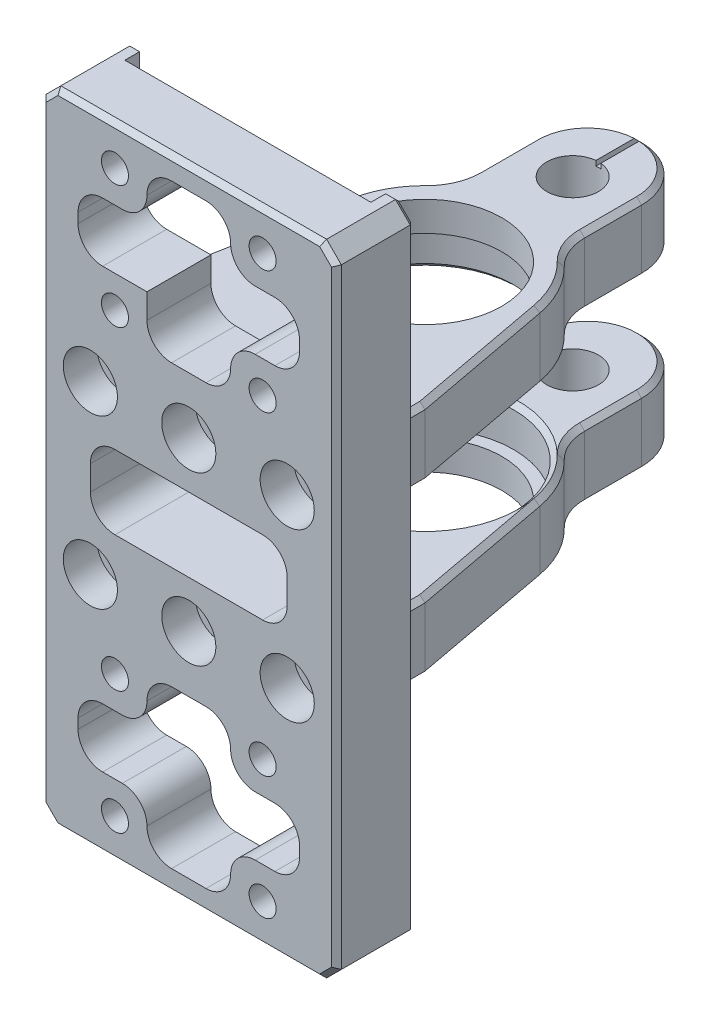
SolidWorks part; units mm, degrees
material "Q235-A"
ref_plane "前视基准面" through (0, 0, 0) normal (0, 0, 1) x (1, 0, 0)
ref_plane "上视基准面" through (0, 0, 0) normal (0, 1, 0) x (1, 0, 0)
ref_plane "右视基准面" through (0, 0, 0) normal (1, 0, 0) x (0, 0, -1)
sketch "草图1" plane through (0, 0, 0) normal (0, 0, 1) x (1, 0, 0)
  line L1 (-30, 65) -> (30, 65)
  line L2 (-30, 65) -> (-30, -65)
  line L3 (-30, -65) -> (30, -65)
  line L4 (30, 65) -> (30, -65)
  line L5 (-30, 65) -> (30, -65) construction
  line L6 (-30, -65) -> (30, 65) construction
  point P0 (0, 0)
  dimension "D1" = 60
  dimension "D2" = 130
extrude "凸台-拉伸1" add sketch "草图1" along normal blind 16
sketch "草图2" plane through (0, 0, 0) normal (0, 0, -1) x (-1, 0, 0)
  line L0 (0, -37.5) -> (0, 37.5) construction
  line L1 (30, -65) -> (-30, -65) construction
  line L2 (25, -65) -> (-25, -65)
  line L3 (25, -65) -> (25, -10)
  line L4 (25, -10) -> (-25, -10)
  line L5 (-25, -65) -> (-25, -10)
  line L6 (25, -65) -> (-25, -10) construction
  line L7 (25, -10) -> (-25, -65) construction
  line L8 (25, 10) -> (-25, 10)
  line L9 (25, 10) -> (25, 65)
  line L10 (25, 65) -> (-25, 65)
  line L11 (-25, 10) -> (-25, 65)
  line L12 (25, 10) -> (-25, 65) construction
  line L13 (25, 65) -> (-25, 10) construction
  point P4 (0, 0)
  dimension "D1" = 20
  dimension "D3" = 50
extrude "切除-拉伸1" cut sketch "草图2" against normal blind 3
sketch "草图14" plane through (0, 0, 0) normal (0, 0, -1) x (-1, 0, 0)
  circle A0 centre (-25, -10) radius 2.5
  circle A1 centre (-25, 10) radius 2.5
  circle A2 centre (25, 10) radius 2.5
  circle A3 centre (25, -10) radius 2.5
  dimension "D1" = 5
extrude "切除-拉伸5" cut sketch "草图14" against normal up to surface (3 mm away) up to face at (0, -37.5, 3)
sketch "草图4" plane through (0, 10, 0) normal (0, 1, 0) x (1, 0, 0)
  line L0 (25, -3) -> (25, 7)
  line L1 (-25, -3) -> (-25, 7)
  line L2 (25, -3) -> (-25, -3)
  line L3 (0, -3) -> (0, 32) construction
  line L4 (25, 7) -> (19.6619, 35.6619)
  line L5 (-25, 7) -> (-19.6619, 35.6619)
  arc A0 (19.6619, 35.6619) -> (-19.6619, 35.6619) centre (0, 32) ccw
  arc A1 (0, 12) -> (19.6619, 35.6619) centre (0, 32) ccw construction
  arc A2 (-19.6619, 35.6619) -> (0, 12) centre (0, 32) ccw construction
  dimension "D2" = 40
  dimension "D1" = 10
  dimension "D3" = 35
extrude "凸台-拉伸2" add sketch "草图4" along normal blind 14 separate body
sketch "草图7" plane through (0, 24, 0) normal (0, 1, 0) x (1, 0, 0)
  line L0 (0, 39) -> (0, 65) construction
  line L1 (-11, 39) -> (-11, 65)
  line L2 (11, 39) -> (11, 65)
  arc A0 (19.6619, 35.6619) -> (-19.6619, 35.6619) centre (0, 32) ccw construction
  arc A1 (-11, 39) -> (11, 39) centre (0, 39) ccw
  arc A2 (11, 65) -> (-11, 65) centre (0, 65) ccw
  point P7 (0, 52)
  dimension "D1" = 26
  dimension "D2" = 22
extrude "凸台-拉伸3" add sketch "草图7" against normal up to surface (14 mm away) up to face at (0, 10, -15.9437)
fillet "圆角1" radius 10 2 edges at (-11, 17, -48.7033) (11, 17, -48.7033)
sketch "草图5" plane through (0, 10, 0) normal (0, -1, 0) x (1, 0, 0)
  circle A0 centre (0, -32) radius 18
  dimension "D1" = 36
extrude "切除-拉伸2" cut sketch "草图5" against normal blind 8
sketch "草图6" plane through (0, 18, 0) normal (0, -1, 0) x (1, 0, 0)
  circle A0 centre (0, -32) radius 15.6
  dimension "D1" = 31.2
extrude "切除-拉伸3" cut sketch "草图6" against normal through all
hole_wizard "M12x1.5 螺纹孔1" positions "草图11" profile "草图12" tap size "M12x1.5" standard "GB"
sketch "草图11" plane through (0, 24, 0) normal (0, 1, 0) x (1, 0, 0)
  circle A0 centre (0, 32) radius 15.6 construction
  point P0 (0, 62)
  dimension "D1" = 30
sketch "草图12" plane through (0, 24, -62) normal (1, 0, 0) x (0, 0, 1)
  line L0 (0, 0) -> (0, 31.6545)
  line L1 (0, 31.6545) -> (5.25, 28.5)
  line L2 (5.25, 28.5) -> (5.25, 0)
  line L5 (5.25, 0) -> (0, 0)
  line L10 (0, 31.6545) -> (-5.25, 28.5) construction
  line L11 (0, -6.35) -> (0, 107.95) construction
  dimension "螺纹孔钻头直径" = 10.5
  dimension "螺纹孔钻头深度" = 28.5
  dimension "导头角度" = 118
cosmetic thread "孔螺蚊线1" parameters "D1"=24, "D2"=12
sketch "草图13" plane through (0, 24, 0) normal (0, 1, 0) x (1, 0, 0)
  line L0 (0, 84.75) -> (0, 67.25) construction
  line L1 (0.5, 84.75) -> (0.5, 67.25)
  line L2 (-0.5, 84.75) -> (-0.5, 67.25)
  arc A0 (11, 65) -> (-11, 65) centre (0, 65) ccw construction
  circle A1 centre (0, 62) radius 5.25 construction
  arc A2 (0.5, 84.75) -> (-0.5, 84.75) centre (0, 84.75) ccw
  arc A3 (-0.5, 67.25) -> (0.5, 67.25) centre (0, 67.25) ccw
  point P8 (0, 76)
  dimension "D1" = 1
extrude "切除-拉伸4" cut sketch "草图13" against normal blind 1
mirror "镜向2" about plane through (0, 0, 0) normal (0, 1, 0) of bodies 122 114
cosmetic thread "孔螺蚊线2" parameters "D1"=24, "D2"=12
hole_wizard "打孔尺寸(%根据)内六角圆柱头螺钉的类型1" positions "草图16" profile "草图17" counterbore size "M6" standard "GB"
sketch "草图16" plane through (0, 0, 16) normal (0, 0, 1) x (1, 0, 0)
  line L0 (-25, 10) -> (25, 10) construction
  line L1 (-25, 24) -> (25, 24) construction
  line L2 (-25, -10) -> (25, -10) construction
  line L3 (-25, -24) -> (25, -24) construction
  line L4 (-25, 10) -> (25, 10) construction
  line L5 (-25, 24) -> (25, 24) construction
  line L6 (-25, -10) -> (25, -10) construction
  line L7 (-25, -24) -> (25, -24) construction
  line L8 (0, -24) -> (0, -10) construction
  line L10 (0, 10) -> (0, 24) construction
  line L12 (20, -17) -> (-20, -17) construction
  line L14 (20, 17) -> (-20, 17) construction
  point P0 (-20, -17)
  point P2 (20, -17)
  point P60 (0, -17)
  point P64 (-20, 17)
  point P102 (20, 17)
  point P103 (0, 17)
  dimension "D1" = 40
sketch "草图17" plane through (-20, -17, 16) normal (1, 0, 0) x (0, -1, 0)
  line L0 (0, 0) -> (0, 30.4828)
  line L1 (0, 30.4828) -> (3.3, 28.5)
  line L2 (3.3, 28.5) -> (3.3, 6.8)
  line L3 (3.3, 6.8) -> (5.5, 6.8)
  line L4 (5.5, 6.8) -> (5.5, 0)
  line L5 (5.5, 0) -> (0, 0)
  line L10 (0, 30.4828) -> (-3.3, 28.5) construction
  line L11 (0, -6.35) -> (0, 107.95) construction
  dimension "孔直径" = 6.6
  dimension "孔深度" = 28.5
  dimension "柱形沉头孔直径" = 11
  dimension "柱形沉头孔深度" = 6.8
  dimension "导头角度" = 118
hole_wizard "M6 螺纹孔1" positions "草图18" profile "草图19" tap size "M6" standard "GB"
sketch "草图18" plane through (0, 0, 3) normal (0, 0, 1) x (1, 0, 0)
  point P0 (-20, -17)
  point P3 (0, -17)
  point P6 (20, -17)
sketch "草图19" plane through (-20, -17, 3) normal (1, 0, 0) x (0, -1, 0)
  line L0 (0, 0) -> (0, 16.5022)
  line L1 (0, 16.5022) -> (2.5, 15)
  line L2 (2.5, 15) -> (2.5, 0)
  line L5 (2.5, 0) -> (0, 0)
  line L10 (0, 16.5022) -> (-2.5, 15) construction
  line L11 (0, -6.35) -> (0, 107.95) construction
  dimension "螺纹孔钻头直径" = 5
  dimension "螺纹孔钻头深度" = 15
  dimension "导头角度" = 118
cosmetic thread "孔螺蚊线3" parameters "D1"=12, "D2"=6
cosmetic thread "孔螺蚊线4" parameters "D1"=12, "D2"=6
cosmetic thread "孔螺蚊线5" parameters "D1"=12, "D2"=6
hole_wizard "M6 螺纹孔2" positions "草图20" profile "草图21" tap size "M6" standard "GB"
sketch "草图20" plane through (0, 0, 3) normal (0, 0, 1) x (1, 0, 0)
  point P0 (-20, 17)
  point P3 (0, 17)
  point P6 (20, 17)
sketch "草图21" plane through (-20, 17, 3) normal (1, 0, 0) x (0, -1, 0)
  line L0 (0, 0) -> (0, 16.5022)
  line L1 (0, 16.5022) -> (2.5, 15)
  line L2 (2.5, 15) -> (2.5, 0)
  line L5 (2.5, 0) -> (0, 0)
  line L10 (0, 16.5022) -> (-2.5, 15) construction
  line L11 (0, -6.35) -> (0, 107.95) construction
  dimension "螺纹孔钻头直径" = 5
  dimension "螺纹孔钻头深度" = 15
  dimension "导头角度" = 118
cosmetic thread "孔螺蚊线6" parameters "D1"=12, "D2"=6
cosmetic thread "孔螺蚊线7" parameters "D1"=12, "D2"=6
cosmetic thread "孔螺蚊线8" parameters "D1"=12, "D2"=6
hole_wizard "打孔尺寸(%根据)内六角圆柱头螺钉的类型2" positions "草图23" profile "草图24" counterbore size "M5" standard "GB"
sketch "草图23" plane through (0, 0, 3) normal (0, 0, -1) x (-1, 0, 0)
  line L0 (0, -65) -> (0, -24) construction
  line L1 (-25, -65) -> (25, -65) construction
  line L2 (-5.25, -24) -> (5.25, -24) construction
  line L4 (0, 65) -> (0, 24) construction
  line L5 (25, 65) -> (-25, 65) construction
  line L6 (5.25, 24) -> (-5.25, 24) construction
  line L9 (-15, -57) -> (15, -57) construction
  line L10 (-15, -57) -> (-15, -32) construction
  line L11 (-15, -32) -> (15, -32) construction
  line L12 (15, -57) -> (15, -32) construction
  line L13 (-15, -57) -> (15, -32) construction
  line L14 (-15, -32) -> (15, -57) construction
  line L16 (-15, 32) -> (15, 32) construction
  line L17 (-15, 32) -> (-15, 57) construction
  line L18 (-15, 57) -> (15, 57) construction
  line L19 (15, 32) -> (15, 57) construction
  line L20 (-15, 32) -> (15, 57) construction
  line L21 (-15, 57) -> (15, 32) construction
  point P0 (-15, -57)
  point P2 (15, -57)
  point P4 (-15, 57)
  point P6 (15, 57)
  point P25 (15, -32)
  point P107 (-15, -32)
  point P112 (0, -44.5)
  point P113 (0, -44.5)
  point P228 (-15, 32)
  point P230 (15, 32)
  point P234 (0, 44.5)
  point P235 (0, 44.5)
  dimension "D1" = 25
  dimension "D2" = 30
sketch "草图24" plane through (15, -57, 3) normal (1, 0, 0) x (0, 1, 0)
  line L0 (0, 0) -> (0, 16.6524)
  line L1 (0, 16.6524) -> (2.75, 15)
  line L2 (2.75, 15) -> (2.75, 5.7)
  line L3 (2.75, 5.7) -> (5, 5.7)
  line L4 (5, 5.7) -> (5, 0)
  line L5 (5, 0) -> (0, 0)
  line L10 (0, 16.6524) -> (-2.75, 15) construction
  line L11 (0, -6.35) -> (0, 107.95) construction
  dimension "孔直径" = 5.5
  dimension "孔深度" = 15
  dimension "柱形沉头孔直径" = 10
  dimension "柱形沉头孔深度" = 5.7
  dimension "导头角度" = 118
sketch "草图25" plane through (0, 0, 0) normal (0, 0, -1) x (-1, 0, 0)
  line L0 (-15, -57) -> (15, -32) construction
  line L1 (20, -7.5) -> (-20, -7.5)
  line L2 (20, -7.5) -> (20, 7.5)
  line L3 (20, 7.5) -> (-20, 7.5)
  line L4 (-20, -7.5) -> (-20, 7.5)
  line L5 (20, -7.5) -> (-20, 7.5) construction
  line L6 (20, 7.5) -> (-20, -7.5) construction
  line L7 (-15, 32) -> (15, 57) construction
  line L8 (22.5, -50.5) -> (-22.5, -50.5)
  line L9 (22.5, -50.5) -> (22.5, -38.5)
  line L10 (22.5, -38.5) -> (-22.5, -38.5)
  line L11 (-22.5, -50.5) -> (-22.5, -38.5)
  line L12 (22.5, -50.5) -> (-22.5, -38.5) construction
  line L13 (22.5, -38.5) -> (-22.5, -50.5) construction
  line L15 (22.5, 38.5) -> (-22.5, 38.5)
  line L16 (22.5, 38.5) -> (22.5, 50.5)
  line L17 (22.5, 50.5) -> (-22.5, 50.5)
  line L18 (-22.5, 38.5) -> (-22.5, 50.5)
  line L19 (22.5, 38.5) -> (-22.5, 50.5) construction
  line L20 (22.5, 50.5) -> (-22.5, 38.5) construction
  line L21 (8.5, -60.5) -> (-8.5, -60.5)
  line L22 (8.5, -60.5) -> (8.5, -28.5)
  line L23 (8.5, -28.5) -> (-8.5, -28.5)
  line L24 (-8.5, -60.5) -> (-8.5, -28.5)
  line L25 (8.5, -60.5) -> (-8.5, -28.5) construction
  line L26 (8.5, -28.5) -> (-8.5, -60.5) construction
  line L27 (8.5, 28.5) -> (-8.5, 28.5)
  line L28 (8.5, 28.5) -> (8.5, 60.5)
  line L29 (8.5, 60.5) -> (-8.5, 60.5)
  line L30 (-8.5, 28.5) -> (-8.5, 60.5)
  line L31 (8.5, 28.5) -> (-8.5, 60.5) construction
  line L32 (8.5, 60.5) -> (-8.5, 28.5) construction
  point P0 (0, 0)
  point P10 (0, -44.5)
  point P19 (0, 44.5)
  point P24 (0, -44.5)
  point P29 (0, 44.5)
  dimension "D1" = 15
  dimension "D2" = 40
  dimension "D3" = 12
  dimension "D4" = 45
  dimension "D5" = 32
  dimension "D6" = 17
extrude "切除-拉伸6" cut sketch "草图25" against normal through all contours L24 L10 L22 L23 | L24 L8 L22 L10 | L8 L24 L10 L11 | L24 L21 L22 L8 | L22 L8 L9 L10 | L4 L1 L2 L3 | L30 L27 L28 L15 | L15 L30 L17 L18 | L30 L15 L28 L17 | L28 L15 L16 L17 | L30 L17 L28 L29 region at (0, 0, 0) region at (-15.5, -44.5, 0) region at (0, -55.5, 0) region at (0, -44.5, 0) region at (15.5, -44.5, 0) region at (0, -33.5, 0) region at (-15.5, 44.5, 0) region at (0, 33.5, 0) region at (0, 44.5, 0) region at (15.5, 44.5, 0) region at (0, 55.5, 0)
fillet "圆角2" radius 5 27 edges at (22.5, 50.5, 9.5) (8.5, 50.5, 9.5) (8.5, 60.5, 9.5) (-8.5, 60.5, 9.5) (-8.5, 50.5, 9.5) (-22.5, 50.5, 9.5) (-22.5, 38.5, 9.5) (-8.5, 28.5, 9.5) (8.5, 28.5, 9.5) (8.5, 38.5, 9.5) (22.5, 38.5, 9.5) (8.5, -38.5, 9.5) (8.5, -28.5, 9.5) (-8.5, -38.5, 9.5) (-8.5, -28.5, 9.5) (-22.5, -38.5, 9.5) (-22.5, -50.5, 9.5) (-8.5, -50.5, 9.5) (-8.5, -60.5, 9.5) (8.5, -60.5, 9.5) (8.5, -50.5, 9.5) (22.5, -50.5, 9.5) (22.5, -38.5, 9.5) (-20, -7.5, 8) (-20, 7.5, 8) (20, 7.5, 8) (20, -7.5, 8)
chamfer "倒角1" distance 3 angle 45 4 edges at (-30, 65, 8) (30, 65, 8) (-30, -65, 8) (30, -65, 8)
chamfer "倒角2" distance 1 angle 45 26 edges at (0, -10, 0) (25, -38.75, 0) (26, -65, 0) (28.5, -63.5, 0) (30, 0, 0) (28.5, 63.5, 0) (26, 65, 0) (25, 38.75, 0) (0, 10, 0) (-25, -38.75, 0) (-26, -65, 0) (-28.5, -63.5, 0) (-25, 38.75, 0) (-26, 65, 0) (-28.5, 63.5, 0) (-30, 0, 0) (28.5, -63.5, 16) (0, -65, 16) (-28.5, -63.5, 16) (-30, 0, 16) (-28.5, 63.5, 16) (0, 65, 16) (28.5, 63.5, 16) (30, 0, 16) (0, -65, 3) (0, 65, 3)
chamfer "倒角3" distance 1 angle 45 24 edges at (25, 24, -2) (25, 10, -2) (22.331, 24, -21.331) (17.6489, 24, -41.4084) (11.7805, 24, -49.5513) (11, 24, -59.2121) (7.953, 24, -72.5993) (-7.953, 24, -72.5993) (-11, 24, -59.2121) (-11.7805, 24, -49.5513) (-17.6489, 24, -41.4084) (-25, 24, -2) (-22.331, 24, -21.331) (22.331, 10, -21.331) (17.6489, 10, -41.4084) (11.7805, 10, -49.5513) (11, 10, -59.2121) (0, 10, -76) (-11, 10, -59.2121) (-11.7805, 10, -49.5513) (-17.6489, 10, -41.4084) (-25, 10, -2) (-22.331, 10, -21.331) (18, 10, -32)
chamfer "倒角4" distance 1 angle 45 24 edges at (25, -10, -2) (-25, -10, -2) (18, -10, -32) (-22.331, -10, -21.331) (-17.6489, -10, -41.4084) (-11.7805, -10, -49.5513) (22.331, -10, -21.331) (-11, -10, -59.2121) (17.6489, -10, -41.4084) (0, -10, -76) (11.7805, -10, -49.5513) (11, -10, -59.2121) (7.953, -24, -72.5993) (11, -24, -59.2121) (11.7805, -24, -49.5513) (17.6489, -24, -41.4084) (22.331, -24, -21.331) (25, -24, -2) (-7.953, -24, -72.5993) (-11, -24, -59.2121) (-11.7805, -24, -49.5513) (-17.6489, -24, -41.4084) (-25, -24, -2) (-22.331, -24, -21.331)
